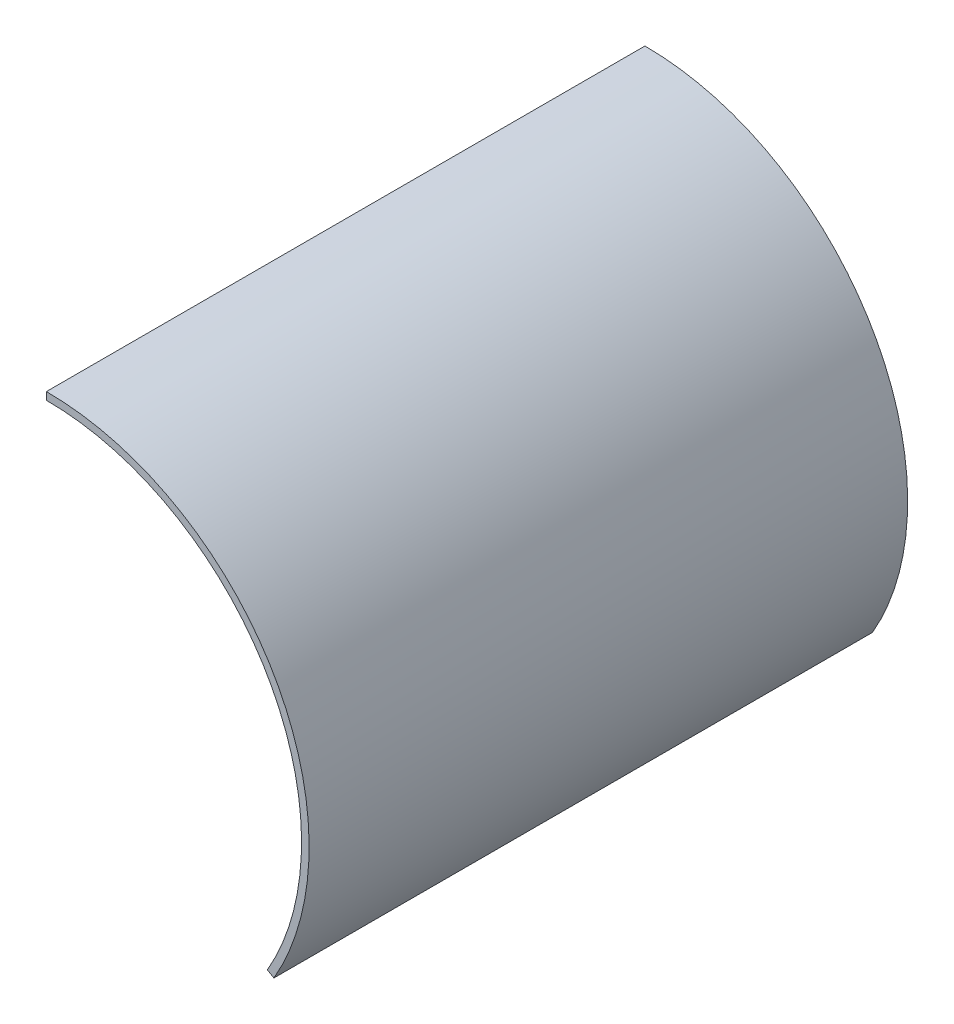
SolidWorks part; units mm, degrees
ref_plane "Front" through (0, 0, 0) normal (0, 0, 1) x (1, 0, 0)
ref_plane "Top" through (0, 0, 0) normal (0, 1, 0) x (1, 0, 0)
ref_plane "Right" through (0, 0, 0) normal (1, 0, 0) x (0, 0, -1)
sketch "Эскиз1" plane through (0, 0, 0) normal (1, 0, 0) x (0, 0, -1)
  line L0 (0, 41.7) -> (0, 40.5)
  line L1 (0, 40.5) -> (95, 40.5)
  line L2 (95, 40.5) -> (95, 41.7)
  line L3 (95, 41.7) -> (0, 41.7)
  line L4 (0, 0) -> (40.5832, 0) construction
  dimension "D1" = 1.2
  dimension "D2" = 40.5
  dimension "D3" = 95
revolve "Повернуть1" add sketch "Эскиз1" angle 120 about L4
